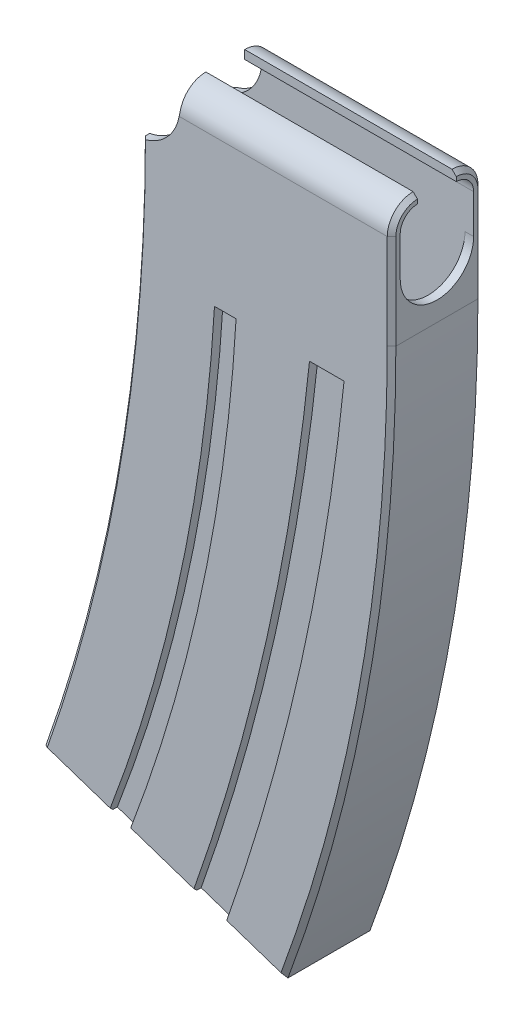
SolidWorks part; units mm, degrees
ref_plane "前视基准面" through (0, 0, 0) normal (0, 0, 1) x (1, 0, 0)
ref_plane "上视基准面" through (0, 0, 0) normal (0, 1, 0) x (1, 0, 0)
ref_plane "右视基准面" through (0, 0, 0) normal (1, 0, 0) x (0, 0, -1)
other "Configuration Table"
sketch "草图1" plane through (0, 0, 0) normal (0, 0, 1) x (1, 0, 0)
  line L0 (0, 0) -> (-49, 0)
  line L1 (0, 0) -> (0, -28)
  line L2 (-25, -167.1941) -> (-81, -148.4568)
  line L3 (-49, 0) -> (-49, -4)
  arc A0 (0, -28) -> (-25, -167.1941) centre (-400, -28) cw
  arc A1 (-49, -4) -> (-58, -14.8167) centre (-60, -4) cw
  arc A2 (-58, -14.8167) -> (-81, -148.4568) centre (-458, -14.7743) cw
  point P11 (-94.987, -169.2204)
  point P12 (-60, -15)
  point P13 (-60.9162, -14.9618)
  point P14 (-81, -150.3255)
  dimension "D3" = 400
  dimension "D5" = 11
  dimension "D6" = 400
  dimension "D1" = 49
  dimension "D2" = 28
  dimension "D4" = 4
  dimension "D7" = 56
  dimension "D8" = 25
  dimension "D9" = 58
  dimension "D10" = 18.5
extrude "凸台-拉伸1" add sketch "草图1" along normal mid plane 21
sketch "草图2" plane through (0, 0, 0) normal (0, 0, 1) x (1, 0, 0)
  line L0 (-81, -148.4568) -> (-25, -167.1941) construction
  line L1 (-65.5, -153.643) -> (-60.7584, -155.2295)
  line L2 (-41, -40) -> (-36, -40)
  line L3 (-19, -40) -> (-11, -40)
  line L4 (-46.0866, -160.1386) -> (-38.5, -162.6771)
  line L5 (0, 0) -> (-49, 0) construction
  line L6 (0, -28) -> (0, 0) construction
  arc A0 (-65.5, -153.643) -> (-41, -40) centre (-421.3331, -17.4674) ccw
  arc A1 (-36, -40) -> (-60.7584, -155.2295) centre (-421.3425, -17.4793) cw
  arc A2 (-19, -40) -> (-46.0866, -160.1386) centre (-536.241, 13.4949) cw
  arc A3 (-11, -40) -> (-38.5, -162.6771) centre (-536.2995, 13.3333) cw
  point P17 (0, 0)
  point P18 (0, 0)
  point P19 (-1.6125, -28.3543)
  dimension "D7" = 38.5
  dimension "D8" = 528
  dimension "D9" = 520
  dimension "D10" = 381
  dimension "D11" = 386
  dimension "D1" = 36
  dimension "D2" = 5
  dimension "D3" = 8
  dimension "D4" = 40
  dimension "D5" = 11
  dimension "D6" = 16.5
extrude "切除-拉伸2" cut sketch "草图2" along normal blind 2 from surface starting at face at (-35.4485, -52.3129, -10.5)
extrude "切除-拉伸3" cut sketch "草图2<2>" against normal blind 2 from surface starting at face at (-35.4485, -52.3129, 10.5)
sketch "草图2<2>" plane through (0, 0, 0) normal (0, 0, 1) x (1, 0, 0) same geometry as "草图2"
fillet "圆角1" radius 6 2 edges at (-24.5, 0, -10.5) (-24.5, 0, 10.5)
shell "抽壳1" thickness 2 removed face at (-49, -1.5505, 0) removed face at (-51.6045, -8.7288, 0.0572)
sketch "草图3" plane through (0, 0, 0) normal (1, 0, 0) x (0, 0, -1)
  line L4 (-4.5, -2) -> (-4.5, 0)
  line L5 (-4.5, 0) -> (4.5, 0)
  line L6 (4.5, 0) -> (4.5, -2)
  line L8 (8.5, -26) -> (8.5, -6)
  line L9 (4.5, -2) -> (-4.5, -2)
  line L10 (-8.5, -6) -> (-8.5, -26)
  line L11 (-8.5, -26) -> (8.5, -26)
  line L12 (8.5, -15) -> (8.5, -6)
  line L14 (-8.5, -6) -> (-8.5, -15)
  arc A2 (-8.5, -15) -> (8.5, -15) centre (0, -15) ccw
  arc A4 (8.5, -6) -> (4.5, -2) centre (4.5, -6) ccw
  arc A5 (-4.5, -2) -> (-8.5, -6) centre (-4.5, -6) ccw
  arc A6 (8.5, -6) -> (4.5, -2) centre (4.5, -6) ccw
  arc A7 (-4.5, -2) -> (-8.5, -6) centre (-4.5, -6) ccw
  dimension "D2" = 15
  dimension "D1" = 2
extrude "切除-拉伸4" cut sketch "草图3" against normal through all
chamfer "倒角1" distance 1 angle 45 7 edges at (-31.75, -164.9356, 10.5) (-53.4225, -157.6841, 10.5) (-73.25, -151.0499, 10.5) (-63.7955, -82.6185, 10.5) (-6.2996, -98.7107, 10.5) (0, -1.7574, 8.7426) (0, -17, 10.5)
chamfer "倒角2" distance 1 angle 45 7 edges at (-63.7955, -82.6185, -10.5) (-73.25, -151.0499, -10.5) (-53.4225, -157.6841, -10.5) (0, -1.7574, -8.7426) (0, -17, -10.5) (-31.75, -164.9356, -10.5) (-6.2996, -98.7107, -10.5)
